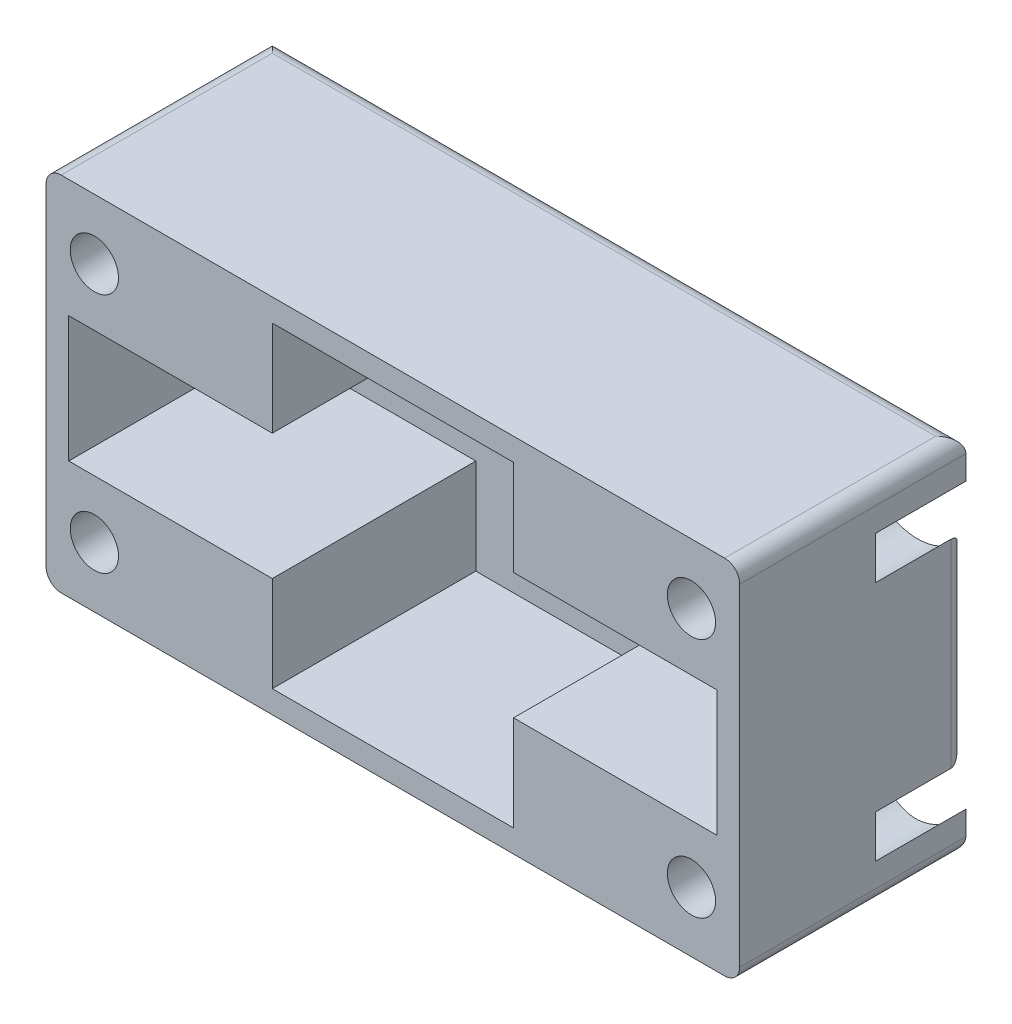
SolidWorks part; units mm, degrees
ref_plane "Front" through (0, 0, 0) normal (0, 0, 1) x (1, 0, 0)
ref_plane "Top" through (0, 0, 0) normal (0, 1, 0) x (1, 0, 0)
ref_plane "Right" through (0, 0, 0) normal (1, 0, 0) x (0, 0, -1)
sketch "Sketch1" plane through (0, 0, 0) normal (0, 0, 1) x (1, 0, 0)
  line L0 (-15.9725, 0) -> (15.4333, 0) construction
  line L1 (11.5, 6) -> (-11.5, 6)
  line L2 (11.5, 6) -> (11.5, -6)
  line L3 (11.5, -6) -> (-11.5, -6)
  line L4 (-11.5, 6) -> (-11.5, -6)
  line L5 (11.5, 6) -> (-11.5, -6) construction
  line L6 (11.5, -6) -> (-11.5, 6) construction
  line L7 (-11.5, -2.087) -> (-4, -2.087)
  line L8 (-11.5, -2.087) -> (-11.5, -6)
  line L9 (-11.5, -6) -> (-4, -6)
  line L10 (-4, -2.087) -> (-4, -6)
  line L11 (0, 9.2145) -> (0, -11.2165) construction
  line L12 (-4, 2.087) -> (-4, 6)
  line L13 (-11.5, 6) -> (-4, 6)
  line L14 (-11.5, 2.087) -> (-11.5, 6)
  line L15 (-11.5, 2.087) -> (-4, 2.087)
  line L16 (11.5, 2.087) -> (4, 2.087)
  line L17 (11.5, 2.087) -> (11.5, 6)
  line L18 (11.5, 6) -> (4, 6)
  line L19 (4, 2.087) -> (4, 6)
  line L20 (4, -2.087) -> (4, -6)
  line L21 (11.5, -6) -> (4, -6)
  line L22 (11.5, -2.087) -> (11.5, -6)
  line L23 (11.5, -2.087) -> (4, -2.087)
  point P0 (0, 0)
  dimension "D1" = 23
  dimension "D2" = 12
  dimension "D3" = 7.5
extrude "Boss-Extrude1" add sketch "Sketch1" along normal blind 7.5 contours L23 L2 L16 L19 L1 L12 L15 L4 L7 L10 L3 L20 | L4 L15 L12 L1 | L19 L16 L2 L1 | L10 L7 L4 L3 | L2 L23 L20 L3 region at (7.75, 4.0435, 0) region at (0, 0, 0) region at (-7.75, 4.0435, 0) region at (7.75, -4.0435, 0) region at (-7.75, -4.0435, 0)
shell "Shell2" thickness 0.75 removed face at (0, 0, 7.5)
extrude "Boss-Extrude2" add sketch "Sketch1<4>" along normal up to surface (7.5 mm away) contours L19 L16 L2 L1 | L14 L15 L12 L13 | L8 L7 L10 L9 | L22 L23 L20 L21 region at (7.75, 4.0435, 0) up to face at (0, 0, 7.5)
sketch "Sketch1<4>" plane through (0, 0, 0) normal (0, 0, 1) x (1, 0, 0) same geometry as "Sketch1"
hole_wizard "Hole2" positions "Sketch4" profile "Sketch5" legacy
sketch "Sketch4" plane through (0, 0, 0) normal (0, 0, -1) x (-1, 0, 0)
  line L0 (13.7314, 4) -> (-13.621, 4) construction
  line L3 (13.2291, -4) -> (-13.6235, -4) construction
  line L6 (-11.5, -6) -> (11.5, -6) construction
  line L7 (-11.5, 6) -> (11.5, 6) construction
  line L8 (11.5, 6) -> (11.5, -6) construction
  line L9 (-11.5, 6) -> (-11.5, -6) construction
  point P16 (9.9, 4)
  point P18 (9.9, -4)
  point P20 (-9.9, 4)
  point P22 (-9.9, -4)
  dimension "D1" = 2
  dimension "D2" = 2
  dimension "D3" = 1.6
  dimension "D4" = 1.6
sketch "Sketch5" plane through (9.9, -4, 0) normal (1, 0, 0) x (0, 1, 0)
  line L0 (0, 0) -> (0, 10)
  line L1 (0, 10) -> (0.8, 10)
  line L2 (0.8, 10) -> (0.8, 3)
  line L3 (0.8, 3) -> (1.75, 3)
  line L4 (1.75, 3) -> (1.75, 0)
  line L5 (1.75, 0) -> (0, 0)
  line L6 (0, 110) -> (0, -10) construction
  dimension "Diameter" = 1.6
  dimension "Depth" = 10
  dimension "C-Bore Diameter" = 3.5
  dimension "C-Bore Depth" = 3
fillet "Fillet1" radius 0.5 8 edges at (-11.5, 6, 3.75) (-11.5, 0, 0) (0, 6, 0) (11.5, 6, 3.75) (11.5, 0, 0) (0, -6, 0) (-11.5, -6, 3.75) (11.5, -6, 3.75)
